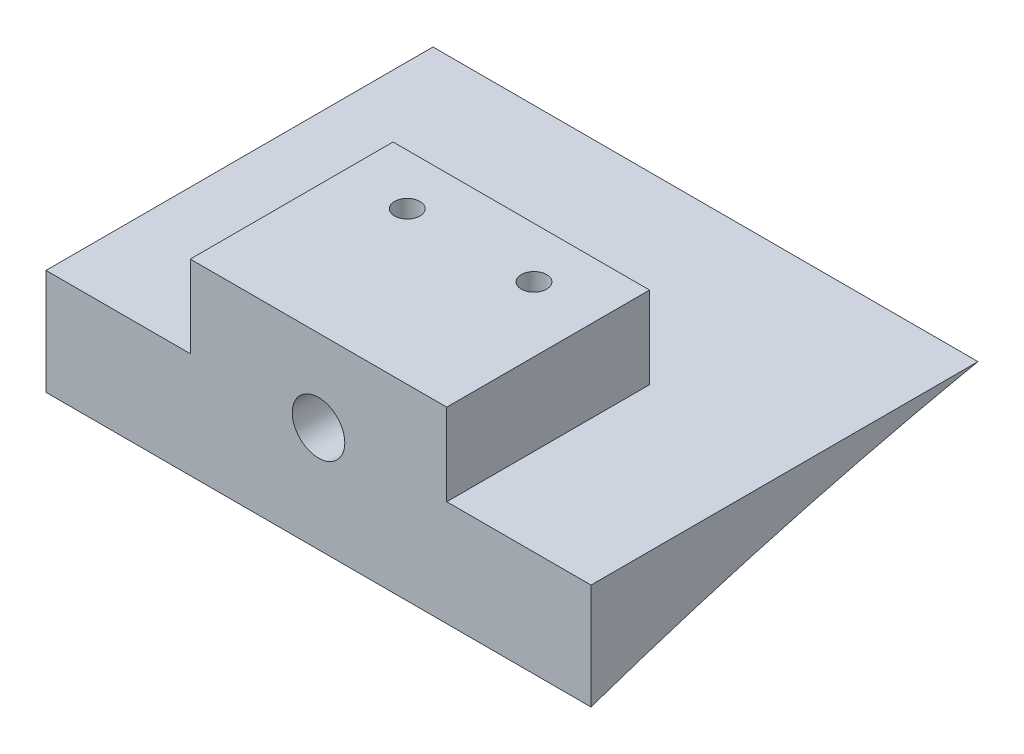
SolidWorks part; units mm, degrees
material "ABS"
ref_plane "Front Plane" through (0, 0, 0) normal (0, 0, 1) x (1, 0, 0)
ref_plane "Top Plane" through (0, 0, 0) normal (0, 1, 0) x (1, 0, 0)
ref_plane "Right Plane" through (0, 0, 0) normal (1, 0, 0) x (0, 0, -1)
curve "Curve1"
  spline degree 3 poles (0, 0.0012, 1.0003) (0, 0.0015, 0.9994) (0, 0.0028, 0.9958) (0, 0.0055, 0.9879) (0, 0.0099, 0.9747) (0, 0.0159, 0.9565) (0, 0.0233, 0.9333) (0, 0.0318, 0.9054) (0, 0.0411, 0.8731) (0, 0.051, 0.8366) (0, 0.0612, 0.7964) (0, 0.0713, 0.7528) (0, 0.0811, 0.7063) (0, 0.0903, 0.6574) (0, 0.0985, 0.6067) (0, 0.1057, 0.5546) (0, 0.1115, 0.5018) (0, 0.1158, 0.4488) (0, 0.1186, 0.3959) (0, 0.1189, 0.3436) (0, 0.1164, 0.2927) (0, 0.1112, 0.2442) (0, 0.1037, 0.1988) (0, 0.0942, 0.157) (0, 0.0831, 0.1194) (0, 0.0711, 0.0865) (0, 0.0584, 0.0585) (0, 0.0457, 0.0357) (0, 0.0334, 0.0184) (0, 0.0218, 0.0064) (0, 0.0108, -0.0005) (0, -0.0003, -0.0011) (0, -0.0092, 0.0055) (0, -0.0148, 0.017) (0, -0.0185, 0.0329) (0, -0.0204, 0.0533) (0, -0.0208, 0.0781) (0, -0.0198, 0.107) (0, -0.0176, 0.1398) (0, -0.0147, 0.176) (0, -0.0111, 0.2153) (0, -0.0074, 0.2574) (0, -0.0037, 0.3019) (0, -0.0005, 0.3484) (0, 0.002, 0.397) (0, 0.0037, 0.4471) (0, 0.0055, 0.4983) (0, 0.0069, 0.5496) (0, 0.0079, 0.6006) (0, 0.0085, 0.6505) (0, 0.0086, 0.699) (0, 0.0083, 0.7455) (0, 0.0076, 0.7894) (0, 0.0065, 0.8302) (0, 0.0053, 0.8675) (0, 0.0039, 0.9007) (0, 0.0027, 0.9296) (0, 0.0013, 0.9539) (0, 0.0006, 0.9727) (0, -0.0011, 0.9872) (0, 0, 0.9944) (0, -0.002, 0.9999) (0, -0.0005, 1) (0, 0, 1) knots 0 0 0 0 0.001372 0.005465 0.012235 0.021602 0.033461 0.047671 0.064081 0.082496 0.102719 0.124527 0.147676 0.171913 0.196978 0.222597 0.248497 0.274385 0.300041 0.32569 0.350525 0.37428 0.396711 0.417577 0.436654 0.453744 0.46868 0.481329 0.491631 0.499616 0.505546 0.510185 0.514824 0.520702 0.528516 0.538466 0.550543 0.564643 0.580638 0.598345 0.617584 0.638174 0.659922 0.682632 0.706121 0.730727 0.7557 0.780732 0.805564 0.829932 0.85357 0.876213 0.89761 0.917519 0.935698 0.951943 0.966047 0.97784 0.987174 0.993932 0.998018 0.999386 1 1 1 1
sketch "Sketch1" plane through (0, 0, 0) normal (1, 0, 0) x (0, 0, -1)
  line L3 (195.725, 0) -> (-195.725, 0) construction
  line L4 (-258.7498, 26.4626) -> (-355.6872, 26.4626)
  line L5 (-355.6872, 26.4626) -> (-355.6872, 0)
  spline S1 degree 3 poles (-355.6872, 0) (-355.3706, 0.108) (-354.109, 0.5382) (-351.285, 1.5029) (-346.6023, 3.0589) (-336.8154, 6.2519) (-320.4299, 11.2778) (-301.3571, 16.5496) (-283.1673, 21.0862) (-270.1079, 24.0716) (-261.8289, 25.8283) (-258.7498, 26.4626) knots 0 0 0 0 0.001372 0.005465 0.012235 0.021602 0.047671 0.082496 0.102719 0.124527 0.137416 0.137416 0.137416 0.137416
  dimension "D1" = 26.4626
  dimension "D2" = 355.6872
  dimension "D3" = 96.9374
extrude "Boss-Extrude1" add sketch "Sketch1" along normal mid plane 136.525
sketch "Sketch4" plane through (0, 0, 355.6872) normal (0, 0, 1) x (1, 0, 0)
  line L0 (68.2625, 26.4626) -> (-68.2625, 26.4626) construction
  line L1 (-32.1232, 46.9893) -> (32.1232, 46.9893)
  line L2 (-32.1232, 46.9893) -> (-32.1232, 26.4626)
  line L3 (-32.1232, 26.4626) -> (32.1232, 26.4626)
  line L4 (32.1232, 46.9893) -> (32.1232, 26.4626)
  point P6 (0, 26.4626)
extrude "Boss-Extrude2" add sketch "Sketch4" against normal blind 50.8
sketch "Sketch2" plane through (0, 26.4626, 0) normal (0, 1, 0) x (1, 0, 0)
  line L0 (-68.2625, -317.5872) -> (68.2625, -317.5872) construction
  line L1 (-68.2625, -258.7498) -> (-68.2625, -355.6872) construction
  line L2 (68.2625, -258.7498) -> (68.2625, -355.6872) construction
  line L3 (-15.875, -317.5872) -> (-15.875, -258.7498) construction
  line L4 (68.2625, -258.7498) -> (-68.2625, -258.7498) construction
  line L5 (15.875, -317.5872) -> (15.875, -258.7498) construction
  line L6 (-68.2625, -286.8403) -> (-15.875, -286.8403) construction
  line L7 (-15.875, -286.8403) -> (15.875, -286.8403) construction
  line L8 (15.875, -286.8403) -> (68.2625, -286.8403) construction
  line L9 (-32.1232, -355.6872) -> (-68.2625, -355.6872) construction
  circle A0 centre (-15.875, -317.5872) radius 3.175
  circle A1 centre (15.875, -317.5872) radius 3.175
  dimension "D1" = 6.35
  dimension "D2" = 6.35
  dimension "D3" = 31.75
  dimension "D4" = 38.1
extrude "Cut-Extrude1" cut sketch "Sketch2" against normal through all and the other way through all
sketch "Sketch5" plane through (0, 0, 355.6872) normal (0, 0, 1) x (1, 0, 0)
  circle A0 centre (0, 26.4626) radius 6.5828
extrude "Cut-Extrude2" cut sketch "Sketch5" against normal blind 12.7
